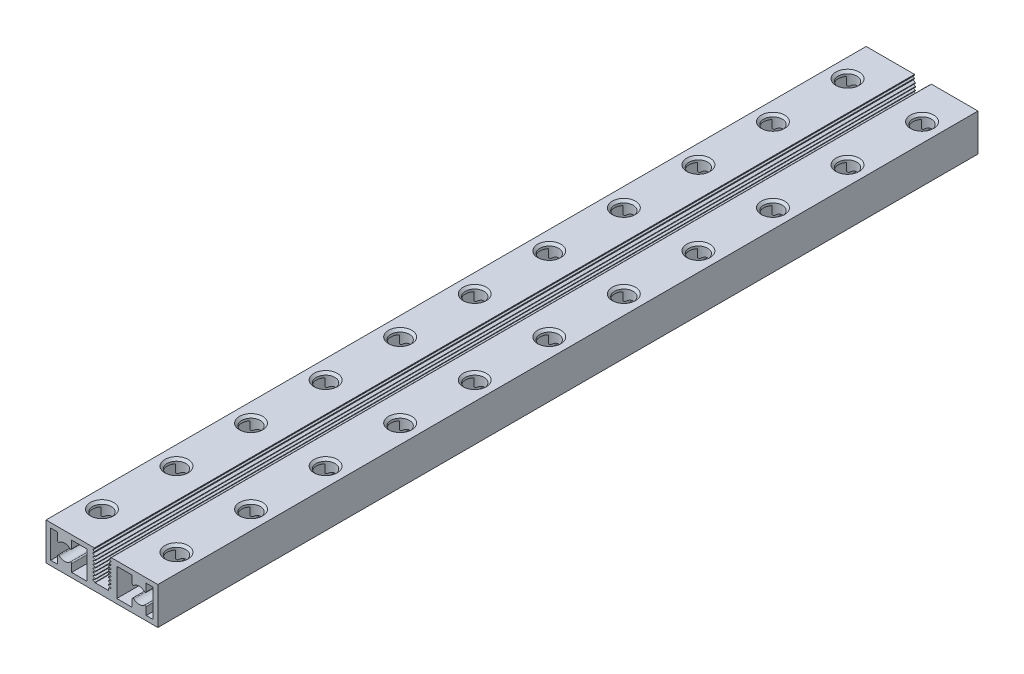
SolidWorks part; units mm, degrees
ref_plane "Front Plane" through (0, 0, 0) normal (0, 0, 1) x (1, 0, 0)
ref_plane "Top Plane" through (0, 0, 0) normal (0, 1, 0) x (1, 0, 0)
ref_plane "Right Plane" through (0, 0, 0) normal (1, 0, 0) x (0, 0, -1)
ref_plane "Plane1" through (0, 8, 0) normal (0, 1, 0) x (1, 0, 0)
sketch "Sketch1" plane through (0, 8, 0) normal (0, 1, 0) x (1, 0, 0)
  line L0 (-12, -176) -> (12, -176)
  line L1 (12, -176) -> (12, 0)
  line L2 (12, 0) -> (-12, 0)
  line L3 (-12, 0) -> (-12, -176)
extrude "Boss-Extrude1" add sketch "Sketch1" against normal blind 8
sketch "Sketch2" plane through (0, 0, 176) normal (0, 0, 1) x (1, 0, 0)
  line L0 (2, 8) -> (-1.62, 8)
  line L1 (-1.62, 8) -> (-1.62, 7.825)
  line L2 (-1.62, 7.825) -> (-2.0747, 7.5625)
  line L3 (-2.0747, 7.5625) -> (-1.4684, 7.2125)
  line L4 (-1.4684, 7.2125) -> (-2.0878, 6.8549)
  line L5 (-2.0878, 6.8549) -> (-1.2404, 6.5125)
  line L6 (-1.2404, 6.5125) -> (-2.1067, 6.1625)
  line L7 (-2.1067, 6.1625) -> (-1.2404, 5.8125)
  line L8 (-1.2404, 5.8125) -> (-2.1067, 5.4625)
  line L9 (-2.1067, 5.4625) -> (-1.2404, 5.1125)
  line L10 (-1.2404, 5.1125) -> (-2.1067, 4.7625)
  line L11 (-2.1067, 4.7625) -> (-1.2404, 4.4125)
  line L12 (-1.2404, 4.4125) -> (-2.1067, 4.0625)
  line L13 (-2.1067, 4.0625) -> (-1.2404, 3.7125)
  line L14 (-1.2404, 3.7125) -> (-2.1067, 3.3625)
  line L15 (-2.1067, 3.3625) -> (-1.2404, 3.0125)
  line L16 (-1.2404, 3.0125) -> (-2.1067, 2.6625)
  line L17 (-2.1067, 2.6625) -> (-1.2404, 2.3125)
  line L18 (-1.2404, 2.3125) -> (-2.1067, 1.9625)
  line L19 (-2.1067, 1.9625) -> (-1.46, 1.7012)
  line L20 (-1.46, 1.7012) -> (-1.46, 1.6)
  line L21 (-1.46, 1.6) -> (1.46, 1.6)
  line L22 (1.46, 1.6) -> (1.46, 2.0618)
  line L23 (1.46, 2.0618) -> (2.1067, 2.3231)
  line L24 (2.1067, 2.3231) -> (1.2404, 2.6731)
  line L25 (1.2404, 2.6731) -> (2.1067, 3.0231)
  line L26 (2.1067, 3.0231) -> (1.2404, 3.3731)
  line L27 (1.2404, 3.3731) -> (2.1067, 3.7231)
  line L28 (2.1067, 3.7231) -> (1.2404, 4.0731)
  line L29 (1.2404, 4.0731) -> (2.1067, 4.4231)
  line L30 (2.1067, 4.4231) -> (1.2404, 4.7731)
  line L31 (1.2404, 4.7731) -> (2.1067, 5.1231)
  line L32 (2.1067, 5.1231) -> (1.2404, 5.4731)
  line L33 (1.2404, 5.4731) -> (2.1067, 5.8231)
  line L34 (2.1067, 5.8231) -> (1.2404, 6.1731)
  line L35 (1.2404, 6.1731) -> (2.0878, 6.5155)
  line L36 (2.0878, 6.5155) -> (1.4684, 6.8731)
  line L37 (1.4684, 6.8731) -> (2.0747, 7.2231)
  line L38 (2.0747, 7.2231) -> (1.4684, 7.5731)
  line L39 (1.4684, 7.5731) -> (2, 7.88)
  line L40 (2, 7.88) -> (2, 8)
extrude "Cut-Extrude1" cut sketch "Sketch2" against normal through all
sketch "Sketch3" plane through (0, 0, 0) normal (0, 0, -1) x (-1, 0, 0)
  line L0 (-6.5, 2.6144) -> (-6.5, 1)
  line L1 (-6.5, 1) -> (-3.2, 1)
  line L2 (-3.2, 1) -> (-3.2, 7)
  line L3 (-3.2, 7) -> (-6.5, 7)
  line L4 (-6.5, 7) -> (-6.5, 5.3856)
  line L5 (-9.5, 5.3856) -> (-9.5, 7)
  line L6 (-9.5, 7) -> (-11, 7)
  line L7 (-11, 7) -> (-11, 1)
  line L8 (-11, 1) -> (-9.5, 1)
  line L9 (-9.5, 1) -> (-9.5, 2.6144)
  arc A0 (-6.5, 5.3856) -> (-6.8368, 5.2398) centre (-6.7, 5.3856) cw
  arc A1 (-6.8368, 5.2398) -> (-9.1632, 5.2398) centre (-8, 4) ccw
  arc A2 (-9.1632, 5.2398) -> (-9.5, 5.3856) centre (-9.3, 5.3856) cw
  arc A3 (-9.5, 2.6144) -> (-9.1632, 2.7602) centre (-9.3, 2.6144) cw
  arc A4 (-9.1632, 2.7602) -> (-6.8368, 2.7602) centre (-8, 4) ccw
  arc A5 (-6.8368, 2.7602) -> (-6.5, 2.6144) centre (-6.7, 2.6144) cw
extrude "Cut-Extrude2" cut sketch "Sketch3" against normal through all
sketch "Sketch4" plane through (0, 0, 176) normal (0, 0, 1) x (1, 0, 0)
  line L0 (-9.5, 7) -> (-11, 7)
  line L1 (-11, 7) -> (-11, 1)
  line L2 (-11, 1) -> (-9.5, 1)
  line L3 (-9.5, 1) -> (-9.5, 2.6144)
  line L4 (-6.5, 2.6144) -> (-6.5, 1)
  line L5 (-6.5, 1) -> (-3.2, 1)
  line L6 (-3.2, 1) -> (-3.2, 7)
  line L7 (-3.2, 7) -> (-6.5, 7)
  line L8 (-6.5, 7) -> (-6.5, 5.3856)
  line L9 (-9.5, 5.3856) -> (-9.5, 7)
  arc A0 (-9.5, 2.6144) -> (-9.1632, 2.7602) centre (-9.3, 2.6144) cw
  arc A1 (-9.1632, 2.7602) -> (-6.8368, 2.7602) centre (-8, 4) ccw
  arc A2 (-6.8368, 2.7602) -> (-6.5, 2.6144) centre (-6.7, 2.6144) cw
  arc A3 (-6.5, 5.3856) -> (-6.8368, 5.2398) centre (-6.7, 5.3856) cw
  arc A4 (-6.8368, 5.2398) -> (-9.1632, 5.2398) centre (-8, 4) ccw
  arc A5 (-9.1632, 5.2398) -> (-9.5, 5.3856) centre (-9.3, 5.3856) cw
extrude "Cut-Extrude3" cut sketch "Sketch4" against normal through all
hole_wizard "Ø4.0 (4) Diameter Hole1" positions "Sketch6" profile "Sketch5" hole size "Ø4.0" standard "ANSI Metric"
sketch "Sketch6" plane through (0, 8, 0) normal (0, 1, 0) x (1, 0, 0)
  point P0 (-8, -152)
  point P1 (-8, -168)
  point P2 (-8, -136)
  point P3 (-8, -120)
  point P4 (-8, -104)
  point P5 (-8, -88)
  point P6 (-8, -72)
  point P7 (-8, -56)
  point P8 (-8, -40)
  point P9 (-8, -24)
  point P10 (-8, -8)
  point P11 (8, -8)
  point P12 (8, -24)
  point P13 (8, -40)
  point P14 (8, -56)
  point P15 (8, -72)
  point P16 (8, -88)
  point P17 (8, -104)
  point P18 (8, -120)
  point P19 (8, -136)
  point P20 (8, -152)
  point P21 (8, -168)
sketch "Sketch5" plane through (-8, 8, 152) normal (1, 0, 0) x (0, 0, 1)
  line L0 (0, 0) -> (0, 10.8144)
  line L1 (0, 10.8144) -> (2, 10.8144)
  line L2 (2, 10.8144) -> (2, 0)
  line L5 (2, 0) -> (0, 0)
  line L10 (0, 10.8144) -> (-2, 10.8144) construction
  line L11 (0, -6.35) -> (0, 107.95) construction
  dimension "Hole Dia." = 4
  dimension "Hole Depth" = 10.8144
  dimension "Drill Angle" = 180
chamfer "Chamfer1" distance 0.5 angle 45 44 edges at (-8, 0, 74) (8, 8, 58) (-8, 8, 106) (-8, 0, 10) (-8, 0, 138) (-8, 8, 170) (8, 8, 122) (-8, 0, 42) (-8, 0, 106) (-8, 0, 170) (-8, 8, 138) (8, 8, 26) (8, 8, 90) (8, 8, 154) (-8, 0, 26) (-8, 0, 58) (-8, 0, 90) (-8, 0, 122) (-8, 0, 154) (-8, 8, 122) (-8, 8, 154) (8, 8, 10) (8, 8, 42) (8, 8, 74) (8, 8, 106) (8, 8, 138) (8, 8, 170) (8, 0, 10) (8, 0, 26) (8, 0, 42) (8, 0, 58) (8, 0, 74) (8, 0, 90) (8, 0, 106) (-8, 8, 10) (8, 0, 122) (-8, 8, 26) (8, 0, 138) (-8, 8, 42) (8, 0, 154) (-8, 8, 58) (8, 0, 170) (-8, 8, 74) (-8, 8, 90)
chamfer "Chamfer2" distance 0.175 angle 60 6 edges at (2.0878, 6.5155, 88) (1.4684, 6.8731, 88) (-1.4684, 7.2125, 88) (-2.0747, 7.5625, 88) (2.0747, 7.2231, 88) (1.4684, 7.5731, 88)
chamfer "Chamfer3" distance 0.169 angle 68 27 edges at (1.2404, 4.7731, 88) (-1.2404, 4.4125, 88) (-1.2404, 5.1125, 88) (2.1067, 5.1231, 88) (2.1067, 4.4231, 88) (-2.1067, 4.0625, 88) (-2.1067, 5.4625, 88) (1.2404, 5.4731, 88) (1.2404, 4.0731, 88) (-1.2404, 3.7125, 88) (-1.2404, 5.8125, 88) (2.1067, 5.8231, 88) (2.1067, 3.7231, 88) (-2.1067, 3.3625, 88) (-2.1067, 6.1625, 88) (1.2404, 6.1731, 88) (1.2404, 3.3731, 88) (-2.1067, 4.7625, 88) (-1.2404, 3.0125, 88) (-1.2404, 6.5125, 88) (2.1067, 3.0231, 88) (-2.1067, 2.6625, 88) (-2.0878, 6.8549, 88) (1.2404, 2.6731, 88) (-1.2404, 2.3125, 88) (2.1067, 2.3231, 88) (-2.1067, 1.9625, 88)
